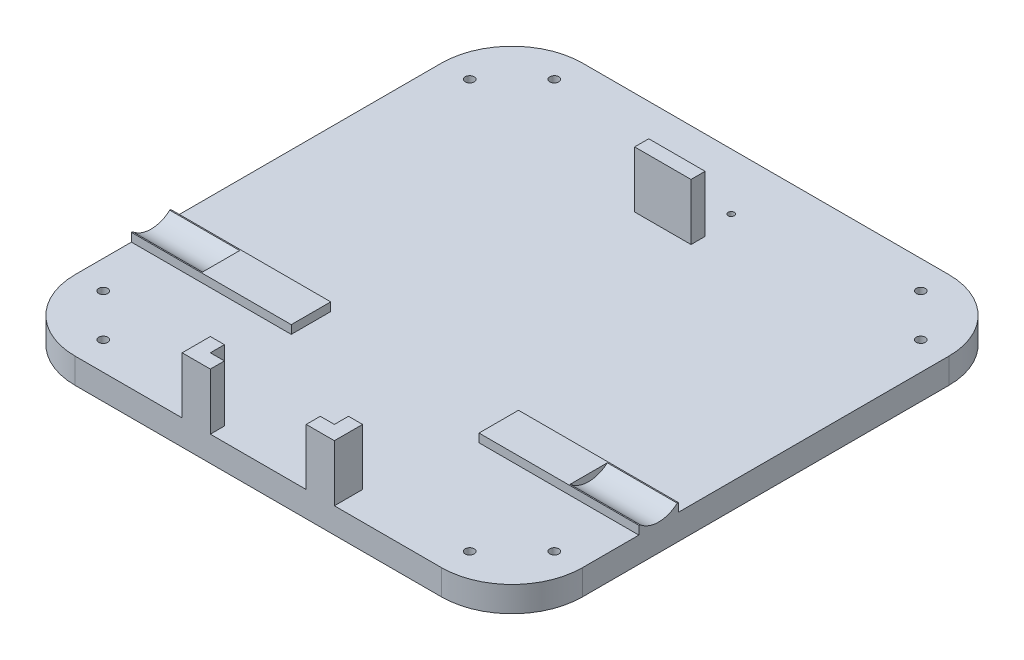
SolidWorks part; units mm, degrees
ref_plane "Front Plane" through (0, 0, 0) normal (0, 0, 1) x (1, 0, 0)
ref_plane "Top Plane" through (0, 0, 0) normal (0, 1, 0) x (1, 0, 0)
ref_plane "Right Plane" through (0, 0, 0) normal (1, 0, 0) x (0, 0, -1)
sketch "Sketch1" plane through (0, 0, 0) normal (0, 1, 0) x (1, 0, 0)
  line L1 (-65, -90) -> (65, -90)
  line L2 (-90, -65) -> (-90, 65)
  line L3 (-65, 90) -> (65, 90)
  line L4 (90, -65) -> (90, 65)
  arc A0 (-90, 65) -> (-65, 90) centre (-65, 65) cw
  arc A1 (65, 90) -> (90, 65) centre (65, 65) cw
  arc A2 (90, -65) -> (65, -90) centre (65, -65) cw
  arc A3 (-65, -90) -> (-90, -65) centre (-65, -65) cw
  point P4 (-90, 0)
  point P6 (0, 90)
  dimension "D3" = 25
  dimension "D1" = 180
  dimension "D2" = 180
extrude "Plate" add sketch "Sketch1" along normal blind 9
sketch "Sketch2" plane through (0, 9, 0) normal (0, 1, 0) x (1, 0, 0)
  line L0 (-7.747, 70) -> (7.747, 70) construction
  line L1 (0, 90) -> (0, 70) construction
  line L2 (-65, 90) -> (65, 90) construction
  circle A1 centre (-7.747, 70) radius 1.09
  circle A2 centre (7.747, 70) radius 1.09
  dimension "D3" = 2.18
  dimension "D1" = 15.494
  dimension "D2" = 20
extrude "Caster Holes" cut sketch "Sketch2" against normal through all
sketch "Sketch3" plane through (0, 9, 0) normal (0, 1, 0) x (1, 0, 0)
  line L0 (-65, 90) -> (-65, -90) construction
  line L1 (65, 90) -> (65, -90) construction
  line L2 (-90, 65) -> (90, 65) construction
  line L3 (-90, -65) -> (90, -65) construction
  circle A0 centre (-65, 80) radius 1.6
  circle A1 centre (-80, 65) radius 1.6
  circle A2 centre (80, 65) radius 1.6
  circle A3 centre (80, -65) radius 1.6
  circle A4 centre (65, 80) radius 1.6
  circle A5 centre (65, -80) radius 1.6
  circle A6 centre (-65, -80) radius 1.6
  circle A7 centre (-80, -65) radius 1.6
  dimension "D1" = 3.2
  dimension "D2" = 15
  dimension "D3" = 15
  dimension "D4" = 15
  dimension "D5" = 15
  dimension "D6" = 15
  dimension "D7" = 15
  dimension "D8" = 15
  dimension "D9" = 15
extrude "Hex Holes" cut sketch "Sketch3" against normal through all
sketch "Sketch4" plane through (0, 9, 0) normal (0, 1, 0) x (1, 0, 0)
  line L0 (-27, -90) -> (-27, -80)
  line L1 (-65, -90) -> (65, -90) construction
  line L2 (-27, -80) -> (-22, -80)
  line L3 (-22, -80) -> (-22, -85)
  line L4 (-22, -85) -> (-17, -85)
  line L5 (-17, -85) -> (-17, -90)
  line L6 (-17, -90) -> (-27, -90)
  line L7 (17, -90) -> (17, -85)
  line L8 (17, -85) -> (22, -85)
  line L9 (22, -85) -> (22, -80)
  line L10 (22, -80) -> (27, -80)
  line L11 (27, -80) -> (27, -90)
  line L12 (27, -90) -> (17, -90)
  line L13 (-10, 58.5) -> (10, 58.5)
  line L14 (10, 58.5) -> (10, 53.5)
  line L15 (10, 53.5) -> (-10, 53.5)
  line L16 (-10, 53.5) -> (-10, 58.5)
  line L17 (-90, -65) -> (-90, 65) construction
  point P20 (0, 53.5)
  dimension "D1" = 5
  dimension "D2" = 44
  dimension "D3" = 63
  dimension "D4" = 20
  dimension "D5" = 5
  dimension "D6" = 138.5
extrude "Boss-Extrude1" add sketch "Sketch4" along normal blind 20
sketch "Sketch5" plane through (0, 9, 0) normal (0, 1, 0) x (1, 0, 0)
  line L0 (-90, -65) -> (-90, 65) construction
  line L1 (-90, -45) -> (-33.3, -45)
  line L2 (-90, -45) -> (-90, -31)
  line L3 (-90, -31) -> (-33.3, -31)
  line L4 (-33.3, -45) -> (-33.3, -31)
  line L5 (90, -65) -> (90, 65) construction
  line L6 (90, -45) -> (33.3, -45)
  line L7 (90, -45) -> (90, -31)
  line L8 (90, -31) -> (33.3, -31)
  line L9 (33.3, -45) -> (33.3, -31)
  line L10 (-65, -90) -> (65, -90) construction
  dimension "D1" = 14
  dimension "D2" = 45
  dimension "D3" = 56.7
extrude "Boss-Extrude2" add sketch "Sketch5" along normal blind 3
sketch "Sketch6" plane through (-90, 0, 0) normal (-1, 0, 0) x (0, 0, 1)
  line L0 (31, 12) -> (45, 12) construction
  line L1 (45, 9) -> (65, 9) construction
  circle A0 centre (38, 19.5) radius 10
  point P2 (0, 0)
  point P5 (38, 12)
  dimension "D1" = 20
  dimension "D2" = 10.5
extrude "Cut-Extrude1" cut sketch "Sketch6" against normal blind 24.8
sketch "Sketch7" plane through (90, 0, 0) normal (1, 0, 0) x (0, 0, -1)
  line L0 (-31, 9) -> (65, 9) construction
  line L1 (-45, 12) -> (-31, 12) construction
  circle A0 centre (-38, 19.5) radius 10
  point P6 (-38, 12)
  dimension "D1" = 20
  dimension "D2" = 10.5
extrude "Cut-Extrude2" cut sketch "Sketch7" against normal blind 24.8
